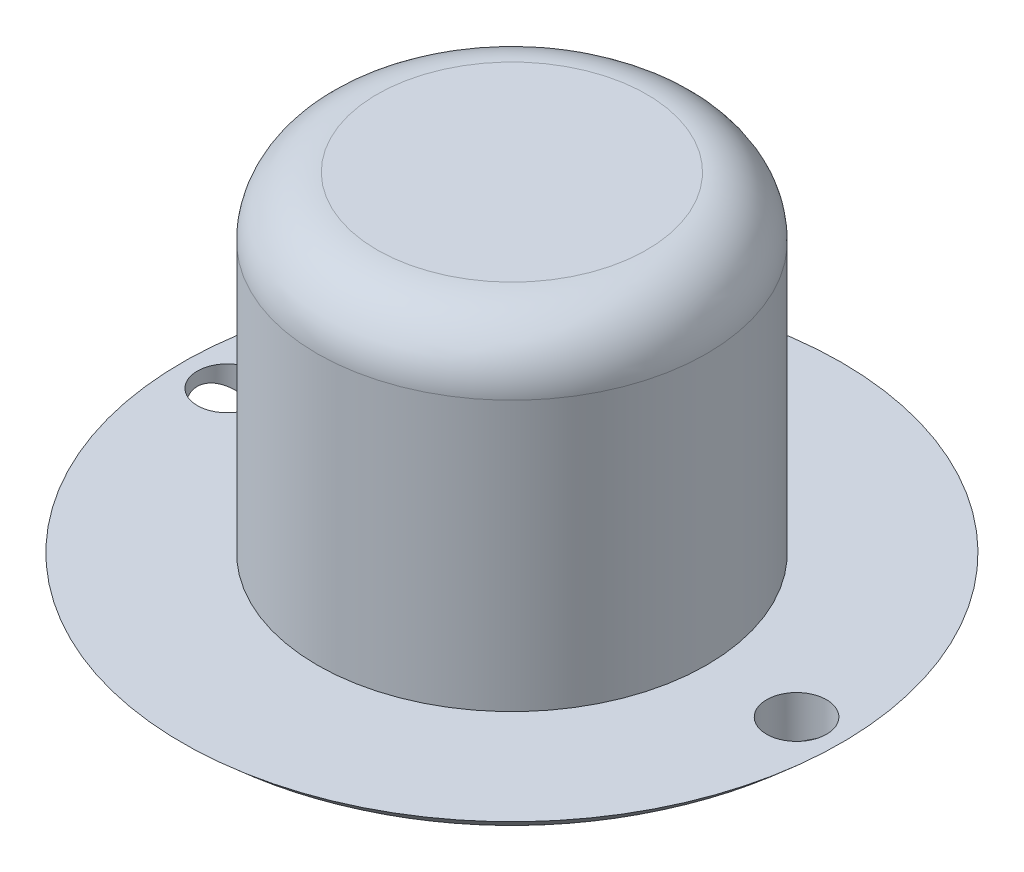
SolidWorks part; units mm, degrees
ref_plane "Front Plane" through (0, 0, 0) normal (0, 0, 1) x (1, 0, 0)
ref_plane "Top Plane" through (0, 0, 0) normal (0, 1, 0) x (1, 0, 0)
ref_plane "Right Plane" through (0, 0, 0) normal (1, 0, 0) x (0, 0, -1)
sketch "Sketch1" plane through (0, 0, 0) normal (0, 1, 0) x (1, 0, 0)
  circle A0 centre (0, 0) radius 6.5
  dimension "D1" = 13
extrude "Boss-Extrude1" add sketch "Sketch1" along normal blind 11
sketch "Sketch2" plane through (0, 0, 0) normal (0, -1, 0) x (1, 0, 0)
  circle A0 centre (0, 0) radius 11
  dimension "D1" = 22
extrude "Boss-Extrude2" add sketch "Sketch2" along normal blind 2
fillet "Fillet1" radius 7 1 edges at (0, -2, -11)
dome "Dome1" faces to dome 1 distance 3 reverse direction no elliptical dome no face at (0, -2, -6.101) parameters "D1"=3
sketch "Sketch3" plane through (0, 0, 0) normal (0, 1, 0) x (1, 0, 0)
  circle A0 centre (0, 0) radius 9.5 construction
  circle A1 centre (-9.5, 0) radius 1
  circle A2 centre (9.5, 0) radius 1
  dimension "D1" = 19
  dimension "D2" = 2
extrude "Cut-Extrude1" cut sketch "Sketch3" against normal blind 2
fillet "Fillet2" radius 2 1 edges at (0, 11, 6.5)
